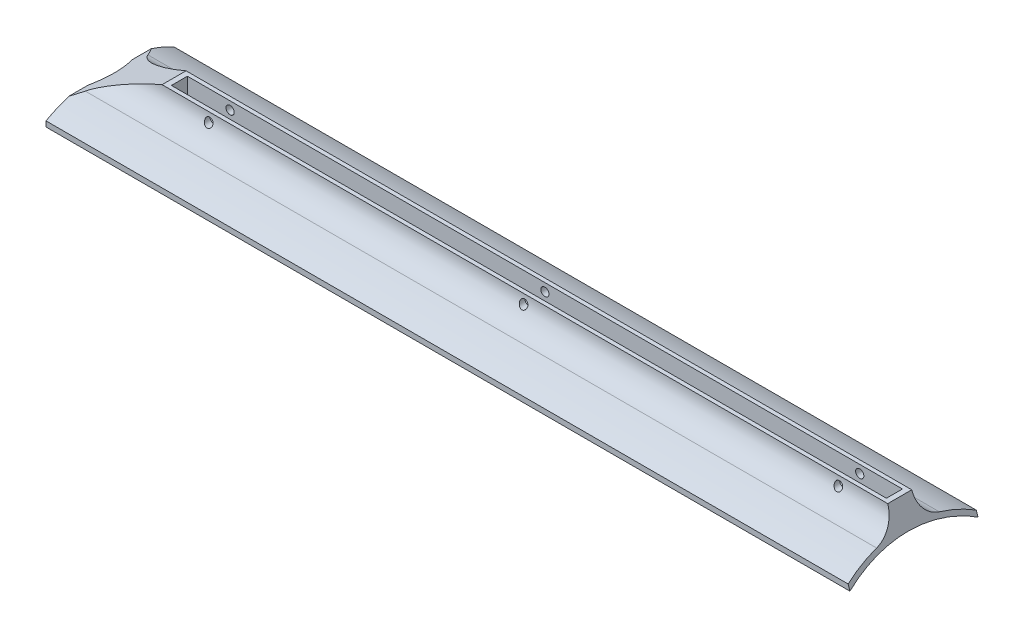
SolidWorks part; units mm, degrees
ref_plane "Front Plane" through (0, 0, 0) normal (0, 0, 1) x (1, 0, 0)
ref_plane "Top Plane" through (0, 0, 0) normal (0, 1, 0) x (1, 0, 0)
ref_plane "Right Plane" through (0, 0, 0) normal (1, 0, 0) x (0, 0, -1)
sketch "Sketch1" plane through (0, 0, 0) normal (1, 0, 0) x (0, 0, -1)
  line L0 (-38.1, -12.7) -> (-38.1, -9.525)
  line L1 (38.1, -12.7) -> (-38.1, -12.7) construction
  line L2 (38.1, -12.7) -> (38.1, 12.7) construction
  line L3 (38.1, 12.7) -> (-38.1, 12.7) construction
  line L4 (-38.1, -12.7) -> (-38.1, 12.7) construction
  line L5 (38.1, -12.7) -> (-38.1, 12.7) construction
  line L6 (38.1, 12.7) -> (-38.1, -12.7) construction
  line L7 (38.1, -12.7) -> (38.1, -9.525)
  line L8 (-7.1374, 12.7) -> (7.1374, 12.7)
  arc A0 (-38.1, -12.7) -> (38.1, -12.7) centre (0, -78.6911) cw
  arc A1 (-38.1, -9.525) -> (-18.661, -1.9622) centre (0, -78.6911) cw
  arc A2 (-7.1374, 12.7) -> (-18.661, -1.9622) centre (-22.227, 12.7) cw
  arc A3 (7.1374, 12.7) -> (18.661, -1.9622) centre (22.227, 12.7) ccw
  arc A4 (18.661, -1.9622) -> (38.1, -9.525) centre (0, -78.6911) cw
  arc A5 (-0.8109, 0.2703) -> (0.8109, 0.2703) centre (0, -78.6911) cw
  point P0 (0, 0)
  point P12 (0, 12.7)
  dimension "D3" = 76.2
  dimension "D1" = 76.2
  dimension "D2" = 25.4
  dimension "D4" = 3.175
  dimension "D5" = 14.2748
extrude "Boss-Extrude1" add sketch "Sketch1" along normal mid plane 508 contours A4 A3 L8 A2 A1 L0 A0 L7 region at (0, 0.6894, 0)
sketch "Sketch2" plane through (0, 0, 38.1) normal (0, 0, 1) x (1, 0, 0)
  line L0 (-254, 12.7) -> (-215.9, 12.7)
  line L1 (254, 12.7) -> (-254, 12.7) construction
  line L2 (-254, 12.7) -> (-254, -3.6322)
  line L3 (-254, 12.7) -> (-254, -1.9622) construction
  line L4 (-254, -3.6322) -> (-215.9, 12.7)
  line L5 (254, -12.7) -> (224.3582, -12.7)
  line L6 (254, -12.7) -> (-254, -12.7) construction
  line L7 (254, 12.7) -> (215.9, 12.7)
  line L8 (215.9, 12.7) -> (224.3582, -12.7)
  line L9 (254, 12.7) -> (254, -12.7)
  dimension "D1" = 38.1
  dimension "D2" = 16.3322
  dimension "D3" = 29.6418
  dimension "D4" = 38.1
extrude "Cut-Extrude1" cut sketch "Sketch2" against normal through all
sketch "Sketch3" plane through (0, 12.7, 0) normal (0, 1, 0) x (1, 0, 0)
  line L1 (215.9, 0) -> (212.725, 0) construction
  line L2 (-212.725, 4.7625) -> (212.725, 4.7625)
  line L3 (-212.725, 4.7625) -> (-212.725, -4.7625)
  line L4 (-212.725, -4.7625) -> (212.725, -4.7625)
  line L5 (212.725, 4.7625) -> (212.725, -4.7625)
  line L6 (-212.725, 4.7625) -> (212.725, -4.7625) construction
  line L7 (-212.725, -4.7625) -> (212.725, 4.7625) construction
  line L8 (215.9, 7.1374) -> (215.9, -7.1374) construction
  point P3 (0, 0)
  dimension "D1" = 3.175
  dimension "D2" = 9.525
extrude "Cut-Extrude2" cut sketch "Sketch3" against normal blind 9.525
sketch "Sketch6" plane through (0, 0, -4.7625) normal (0, 0, 1) x (1, 0, 0)
  line L0 (-212.725, 7.9375) -> (-187.325, 7.9375) construction
  line L1 (-212.725, 3.175) -> (-212.725, 12.7) construction
  line L2 (212.725, 7.9375) -> (187.325, 7.9375) construction
  line L3 (212.725, 3.175) -> (212.725, 12.7) construction
  line L4 (212.725, 12.7) -> (-212.725, 12.7) construction
  line L5 (-212.725, 7.9375) -> (212.725, 7.9375) construction
  line L6 (0, 7.9375) -> (0, 12.7) construction
  circle A0 centre (-187.325, 7.9375) radius 2.4384
  circle A1 centre (187.325, 7.9375) radius 2.4384
  circle A2 centre (0, 7.9375) radius 2.4384
  point P4 (-212.725, 7.9375)
  dimension "D2" = 4.8768
  dimension "D4" = 4.8768
  dimension "D5" = 4.8768
  dimension "D1" = 25.4
  dimension "D3" = 25.4
extrude "Cut-Extrude3" cut sketch "Sketch6" against normal up to surface and the other way up to surface up to face at (-8.327, 4.3723, -11.6312) other way up to face at (-8.327, 4.3723, 11.6312)
ref_plane "Plane1" through (212.725, 12.7, 4.7625) normal (0, 0, -1) x (-1, 0, 0)
